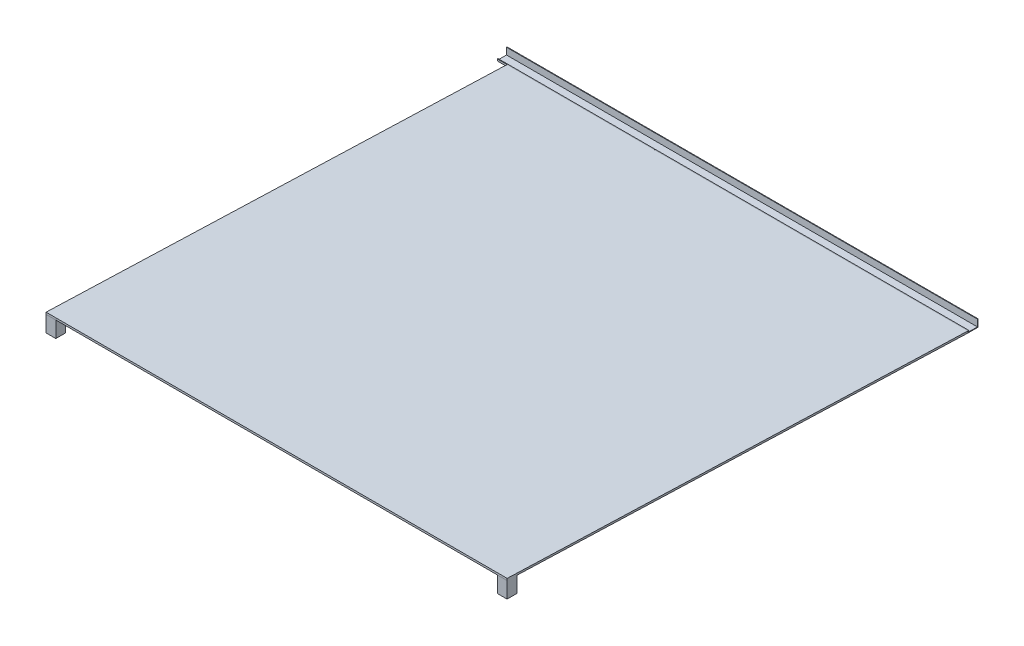
SolidWorks part; units mm, degrees
material "Pine"
ref_plane "Front" through (0, 0, 0) normal (0, 0, 1) x (1, 0, 0)
ref_plane "Top" through (0, 0, 0) normal (0, 1, 0) x (1, 0, 0)
ref_plane "Right" through (0, 0, 0) normal (1, 0, 0) x (0, 0, -1)
sketch "Sketch1" plane through (0, 0, 0) normal (0, 1, 0) x (1, 0, 0)
  line L1 (-2438.4, 2438.4) -> (2438.4, 2438.4) construction
  line L2 (-2438.4, 2438.4) -> (-2438.4, -2438.4) construction
  line L3 (-2438.4, -2438.4) -> (2438.4, -2438.4) construction
  line L4 (2438.4, 2438.4) -> (2438.4, -2438.4) construction
  line L5 (-2438.4, 2438.4) -> (2438.4, -2438.4) construction
  line L6 (-2438.4, -2438.4) -> (2438.4, 2438.4) construction
  point P0 (0, 0)
  dimension "D1" = 4876.8
  dimension "D2" = 4876.8
ref_plane "Plane1" through (0, 0, -2438.4) normal (0, 0, 1) x (1, 0, 0)
ref_plane "Plane2" through (0, 0, 2438.4) normal (0, 0, 1) x (1, 0, 0)
ref_plane "Plane3" through (-2438.4, 0, 0) normal (-1, 0, 0) x (0, 0, 1)
ref_plane "Plane4" through (2438.4, 0, 0) normal (-1, 0, 0) x (0, 0, 1)
sketch "Sketch2" plane through (2438.4, 0, 0) normal (-1, 0, 0) x (0, 0, 1)
  line L0 (-2336.8, 0) -> (-1015.3811, 46.145)
  line L1 (-2438.4, 0) -> (2438.4, 0) construction
  line L2 (-1015.3811, 46.145) -> (1015.3811, 117.0607)
  line L3 (1015.3811, 117.0607) -> (2438.4, 166.7537)
  line L4 (2438.4, -2682.24) -> (2438.4, 2682.24) construction
  line L5 (2438.4, 0) -> (-2438.4, 0) construction
  line L6 (0, 0) -> (0, 81.6029) construction
  line L7 (-2438.4, -2682.24) -> (-2438.4, 2682.24) construction
  dimension "D1" = 2
  dimension "D2" = 2032
  dimension "D4" = 101.6
extrude "Extrude-Thin1" add sketch "Sketch2" along normal blind 4775.2 thin thin type one direction reverse wall 19.05
sketch "Sketch3" plane through (0, 0, 0) normal (0, 1, 0) x (1, 0, 0)
  line L13 (-2336.8, -2438.4) -> (-2235.2, -2438.4)
  line L14 (-2336.8, -2438.4) -> (-2336.8, -2336.8)
  line L15 (-2336.8, -2336.8) -> (-2235.2, -2336.8)
  line L16 (-2235.2, -2438.4) -> (-2235.2, -2336.8)
  line L21 (2438.4, -2438.4) -> (2336.8, -2438.4)
  line L22 (2438.4, -2438.4) -> (2438.4, -2336.8)
  line L23 (2438.4, -2336.8) -> (2336.8, -2336.8)
  line L24 (2336.8, -2438.4) -> (2336.8, -2336.8)
extrude "Boss-Extrude1" add sketch "Sketch3" along normal up to surface (166.7537 mm away) up to face at (50.8, 83.3768, 50.8)
sketch "Sketch5" plane through (-2438.4, 0, 0) normal (-1, 0, 0) x (0, 0, 1)
  line L0 (-2438.4, 76.2) -> (-2438.4, 0)
  line L1 (-2438.4, -2682.24) -> (-2438.4, 2682.24) construction
  line L2 (2438.4, 0) -> (-2438.4, 0) construction
  line L3 (-2438.4, 0) -> (-2337.4648, 0)
  line L4 (-2337.4648, 0) -> (-2337.4648, 19.05)
  line L5 (-2337.4648, 19.05) -> (-2343.8148, 19.05)
  line L6 (-2343.8148, 19.05) -> (-2343.8148, 6.35)
  line L7 (-2343.8148, 6.35) -> (-2432.05, 6.35)
  line L8 (-2432.05, 6.35) -> (-2432.05, 76.2)
  line L9 (-2432.05, 76.2) -> (-2438.4, 76.2)
  line L10 (-2343.8148, 6.35) -> (-2343.8148, 0) construction
  dimension "D1" = 6.35
  dimension "D2" = 76.2
  dimension "D3" = 12.7
extrude "Boss-Extrude3" add sketch "Sketch5" against normal up to surface (4876.8 mm away) separate body up to face at (2438.4, 76.3985, 1044.8386)
